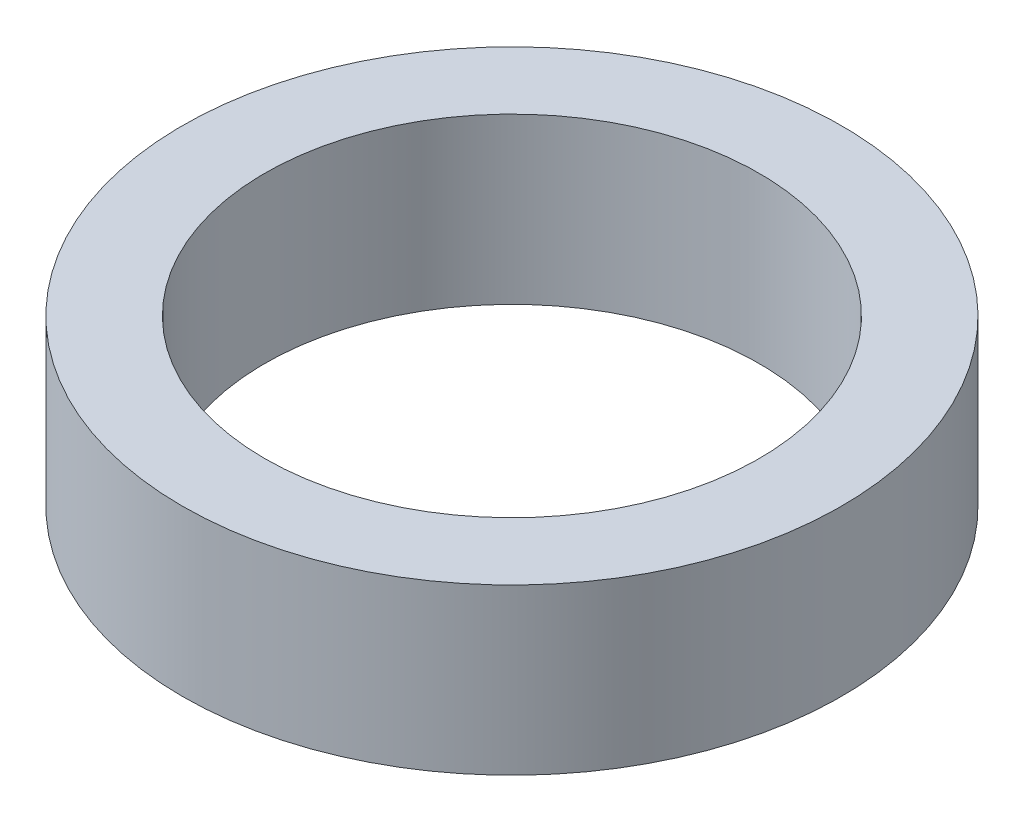
SolidWorks part; units mm, degrees
ref_plane "Front Plane" through (0, 0, 0) normal (0, 0, 1) x (1, 0, 0)
ref_plane "Top Plane" through (0, 0, 0) normal (0, 1, 0) x (1, 0, 0)
ref_plane "Right Plane" through (0, 0, 0) normal (1, 0, 0) x (0, 0, -1)
sketch "Sketch1" plane through (0, 0, 0) normal (0, 1, 0) x (1, 0, 0)
  circle A0 centre (0, 0) radius 4
  circle A1 centre (0, 0) radius 3
extrude "Boss-Extrude1" add sketch "Sketch1" along normal blind 2
